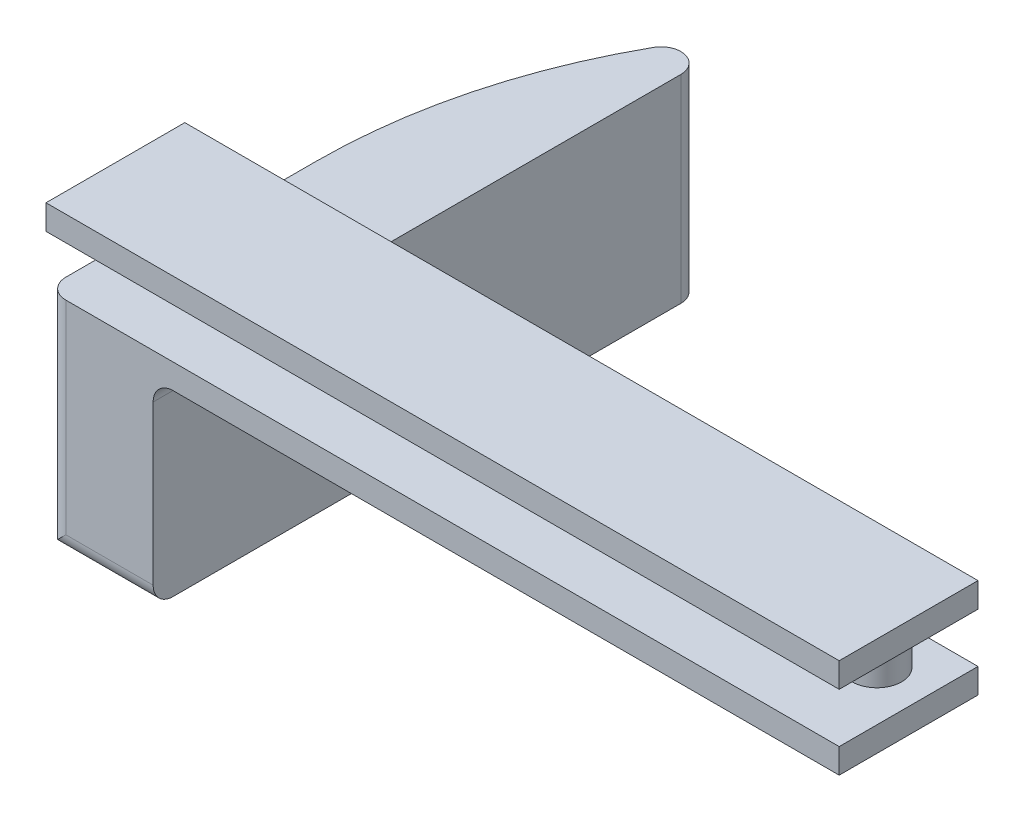
SolidWorks part; units mm, degrees
ref_plane "Front Plane" through (0, 0, 0) normal (0, 0, 1) x (1, 0, 0)
ref_plane "Top Plane" through (0, 0, 0) normal (0, 1, 0) x (1, 0, 0)
ref_plane "Right Plane" through (0, 0, 0) normal (1, 0, 0) x (0, 0, -1)
sketch "Sketch2" plane through (0, 0, 0) normal (0, 1, 0) x (1, 0, 0)
  line L1 (0, 0) -> (101.6, 0)
  line L2 (0, 0) -> (0, 17.78)
  line L3 (0, 17.78) -> (101.6, 17.78)
  line L4 (101.6, 0) -> (101.6, 17.78)
  dimension "D1" = 17.78
  dimension "D2" = 101.6
extrude "Boss-Extrude1" add sketch "Sketch2" along normal blind 3.175
sketch "Sketch3" plane through (0, 0, 0) normal (0, -1, 0) x (1, 0, 0)
  line L0 (95.25, -11.176) -> (6.35, -11.176) construction
  line L1 (95.25, -14.351) -> (6.35, -14.351)
  line L2 (95.25, -8.001) -> (6.35, -8.001)
  line L3 (0, 0) -> (101.6, 0) construction
  line L4 (0, -17.78) -> (0, 0) construction
  arc A0 (95.25, -14.351) -> (95.25, -8.001) centre (95.25, -11.176) ccw
  arc A1 (6.35, -8.001) -> (6.35, -14.351) centre (6.35, -11.176) ccw
  point P2 (50.8, -11.176)
  dimension "D1" = 88.9
  dimension "D2" = 11.176
  dimension "D3" = 6.35
  dimension "D4" = 6.35
extrude "Boss-Extrude2" add sketch "Sketch3" along normal blind 6.35 contours L2 A1 L1 A0
ref_plane "Plane1" through (0, -3.175, 0) normal (0, -1, 0) x (-1, 0, 0)
mirror "Mirror1" about plane through (0, -3.175, 0) normal (0, -1, 0) of "Boss-Extrude1"
sketch "Sketch5" plane through (0, -9.525, 0) normal (0, -1, 0) x (1, 0, 0)
  line L31 (0, 0) -> (13.7244, 0)
  line L32 (0, 0) -> (0, -34.4993)
  line L36 (13.7244, 0) -> (13.7244, -76.2)
  arc A2 (0, -34.4993) -> (13.7244, -76.2) centre (70.2144, -34.4993) ccw
  dimension "D1" = 76.2
extrude "Boss-Extrude3" add sketch "Sketch5" along normal blind 25.4
fillet "Fillet2" radius 2.54 1 edges at (13.7244, -22.225, -76.2)
fillet "Fillet3" radius 2.54 3 edges at (13.7244, -9.525, -8.89) (0, -20.6375, 0) (6.8622, -34.925, 0)
